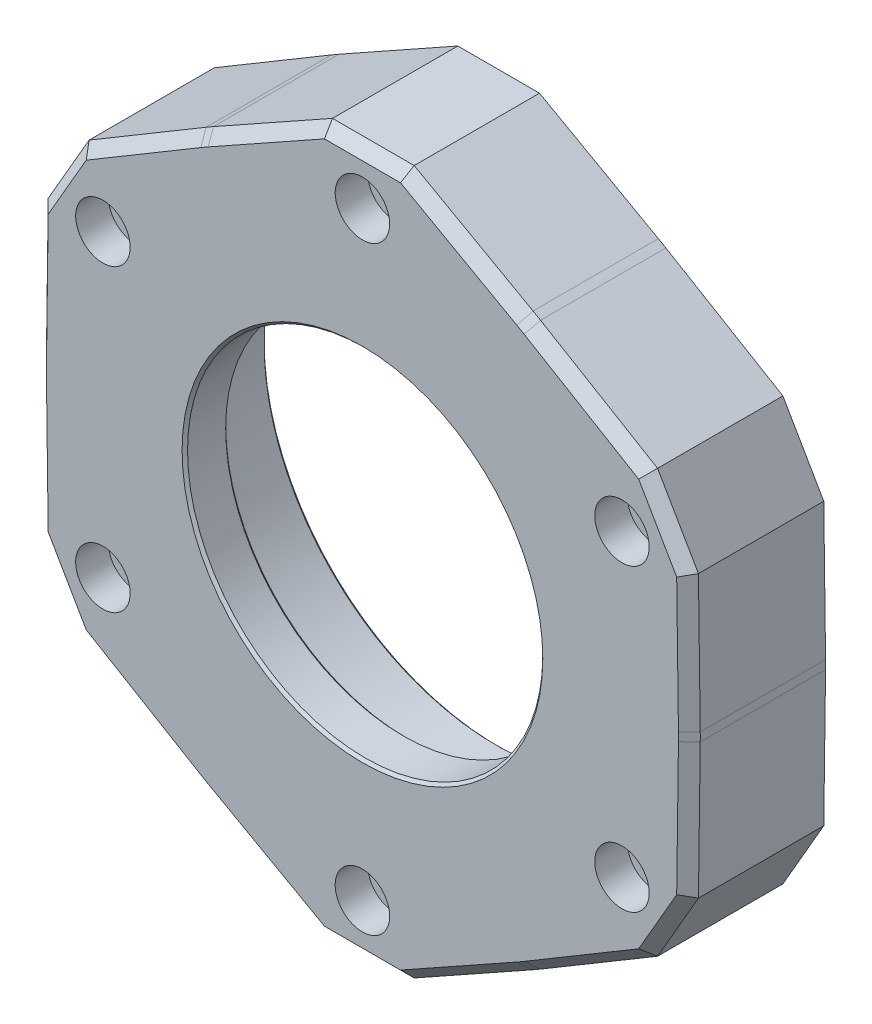
SolidWorks part; units mm, degrees
ref_plane "Front Plane" through (0, 0, 0) normal (0, 0, 1) x (1, 0, 0)
ref_plane "Top Plane" through (0, 0, 0) normal (0, 1, 0) x (1, 0, 0)
ref_plane "Right Plane" through (0, 0, 0) normal (1, 0, 0) x (0, 0, -1)
sketch "Sketch1" plane through (0, 0, 0) normal (0, 0, 1) x (1, 0, 0)
  circle A0 centre (0, 0) radius 60
  circle A1 centre (0, 0) radius 55 construction
  circle A2 centre (0, 55) radius 2.55
  circle A3 centre (47.6314, 27.5) radius 2.55
  circle A4 centre (47.6314, -27.5) radius 2.55
  circle A5 centre (0, -55) radius 2.55
  circle A6 centre (-47.6314, -27.5) radius 2.55
  circle A7 centre (-47.6314, 27.5) radius 2.55
  circle A8 centre (0, 0) radius 42.55
  point P18 (0, 0)
  dimension "D1" = 120
  dimension "D2" = 110
  dimension "D3" = 5.1
  dimension "D5" = 85.1
  dimension "D4" = 6
extrude "Boss-Extrude1" add sketch "Sketch1" along normal blind 25
sketch "Sketch3" plane through (0, 0, 25) normal (0, 0, 1) x (1, 0, 0)
  circle A0 centre (0, 0) radius 42.55
  circle A1 centre (0, 0) radius 32.6
  dimension "D1" = 85.1
  dimension "D2" = 65.2
extrude "Boss-Extrude2" add sketch "Sketch3" against normal blind 8
sketch "Sketch7" plane through (0, 0, 0) normal (0, 0, -1) x (-1, 0, 0)
  line L0 (-29.3133, 52.352) -> (-7.5, 64.5659)
  line L1 (-7.5, 64.5659) -> (7.5, 64.5659)
  line L2 (7.5, 64.5659) -> (29.3133, 52.352)
  line L3 (59.6657, 25.7877) -> (59.9948, 0.7899)
  line L4 (52.1657, 38.7781) -> (59.6657, 25.7877)
  line L5 (30.6815, 51.5621) -> (52.1657, 38.7781)
  line L6 (52.1657, -38.7781) -> (30.6815, -51.5621)
  line L7 (59.6657, -25.7877) -> (52.1657, -38.7781)
  line L8 (59.9948, -0.7899) -> (59.6657, -25.7877)
  line L9 (-7.5, -64.5659) -> (-29.3133, -52.352)
  line L10 (7.5, -64.5659) -> (-7.5, -64.5659)
  line L11 (29.3133, -52.352) -> (7.5, -64.5659)
  line L12 (-59.6657, -25.7877) -> (-59.9948, -0.7899)
  line L13 (-52.1657, -38.7781) -> (-59.6657, -25.7877)
  line L14 (-30.6815, -51.5621) -> (-52.1657, -38.7781)
  line L15 (-52.1657, 38.7781) -> (-30.6815, 51.5621)
  line L16 (-59.6657, 25.7877) -> (-52.1657, 38.7781)
  line L17 (-59.9948, 0.7899) -> (-59.6657, 25.7877)
  circle A0 centre (0, 0) radius 65 construction
  circle A1 centre (0, 0) radius 60 construction
  arc A2 (-30.6815, 51.5621) -> (-59.9948, 0.7899) centre (0, 0) ccw
  arc A3 (29.3133, 52.352) -> (-29.3133, 52.352) centre (0, 0) ccw
  arc A4 (59.9948, 0.7899) -> (30.6815, 51.5621) centre (0, 0) ccw
  arc A5 (30.6815, -51.5621) -> (59.9948, -0.7899) centre (0, 0) ccw
  arc A6 (-29.3133, -52.352) -> (29.3133, -52.352) centre (0, 0) ccw
  arc A7 (-59.9948, -0.7899) -> (-30.6815, -51.5621) centre (0, 0) ccw
  point P8 (0, 64.5659)
  point P35 (0, 0)
  dimension "D1" = 130
  dimension "D2" = 15
  dimension "D3" = 6
extrude "Boss-Extrude3" add sketch "Sketch7" against normal up to surface (25 mm away) up to face at (-45.0814, -27.5, 25)
sketch "Sketch8" plane through (0, 0, 25) normal (0, 0, 1) x (1, 0, 0)
  circle A0 centre (0, 55) radius 5
  circle A1 centre (47.6314, 27.5) radius 5
  circle A2 centre (47.6314, -27.5) radius 5
  circle A3 centre (0, -55) radius 5
  circle A4 centre (-47.6314, -27.5) radius 5
  circle A5 centre (-47.6314, 27.5) radius 5
  point P15 (0, 0)
  dimension "D1" = 10
  dimension "D2" = 6
extrude "Cut-Extrude1" cut sketch "Sketch8" against normal blind 6
chamfer "Chamfer2" distance 0.5 angle 45 3 edges at (42.55, 0, 0) (32.6, 0, 17) (32.6, 0, 25)
chamfer "Chamfer3" distance 2 angle 45 24 edges at (-18.4067, 58.4589, 25) (0, 64.5659, 25) (18.4067, 58.4589, 25) (30, 51.9615, 25) (41.4236, 45.1701, 25) (55.9157, 32.2829, 25) (59.8302, 13.2888, 25) (60, 0, 25) (59.8302, -13.2888, 25) (55.9157, -32.2829, 25) (41.4236, -45.1701, 25) (30, -51.9615, 25) (18.4067, -58.4589, 25) (0, -64.5659, 25) (-18.4067, -58.4589, 25) (-30, -51.9615, 25) (-41.4236, -45.1701, 25) (-55.9157, -32.2829, 25) (-59.8302, -13.2888, 25) (-60, 0, 25) (-59.8302, 13.2888, 25) (-55.9157, 32.2829, 25) (-41.4236, 45.1701, 25) (-30, 51.9615, 25)
sketch "Sketch9" plane through (0, 0, 0) normal (0, 0, -1) x (-1, 0, 0)
  line L0 (0, 47.96) -> (0, 0) construction
  line L1 (0, 0) -> (-8.3282, 47.2314) construction
  circle A55 centre (0, 0) radius 47.96 construction
  circle A56 centre (-8.3282, 47.2314) radius 2.025
  circle A57 centre (8.3282, 47.2314) radius 2.025
  circle A58 centre (23.98, 41.5346) radius 2.025
  circle A59 centre (36.7395, 30.8281) radius 2.025
  circle A60 centre (45.0677, 16.4033) radius 2.025
  circle A61 centre (47.96, 0) radius 2.025
  circle A62 centre (45.0677, -16.4033) radius 2.025
  circle A63 centre (36.7395, -30.8281) radius 2.025
  circle A64 centre (23.98, -41.5346) radius 2.025
  circle A65 centre (8.3282, -47.2314) radius 2.025
  circle A66 centre (-8.3282, -47.2314) radius 2.025
  circle A67 centre (-23.98, -41.5346) radius 2.025
  circle A68 centre (-36.7395, -30.8281) radius 2.025
  circle A69 centre (-45.0677, -16.4033) radius 2.025
  circle A70 centre (-47.96, 0) radius 2.025
  circle A71 centre (-45.0677, 16.4033) radius 2.025
  circle A72 centre (-36.7395, 30.8281) radius 2.025
  circle A73 centre (-23.98, 41.5346) radius 2.025
  point P42 (0, 0)
  point P61 (0, 0)
  point P96 (0, 0)
  dimension "D1" = 95.92
  dimension "D3" = 4.05
  dimension "D4" = 18
  dimension "D2" = 10
extrude "Cut-Extrude2" cut sketch "Sketch9" against normal blind 7
